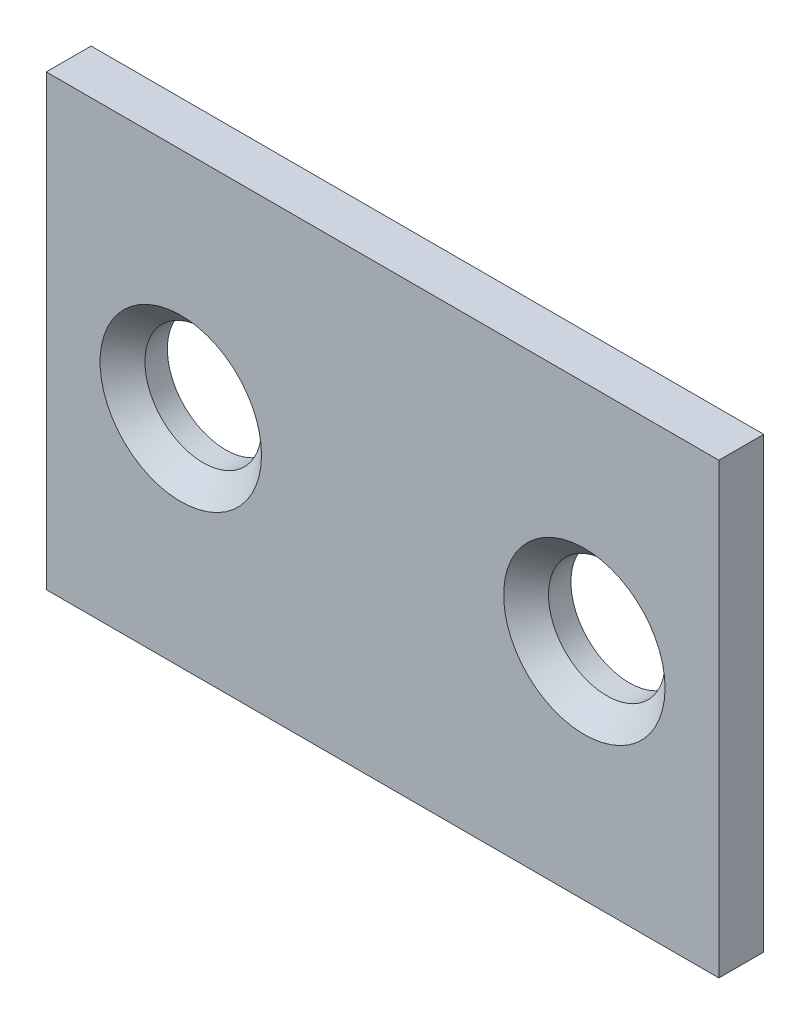
SolidWorks part; units mm, degrees
material "Декапирана стом. ламарина Iгр. 1c"
ref_plane "Front Plane" through (0, 0, 0) normal (0, 0, 1) x (1, 0, 0)
ref_plane "Top Plane" through (0, 0, 0) normal (0, 1, 0) x (1, 0, 0)
ref_plane "Right Plane" through (0, 0, 0) normal (1, 0, 0) x (0, 0, -1)
sketch "Sketch1" plane through (0, 0, 0) normal (0, 0, 1) x (1, 0, 0)
  line L1 (-15, -10) -> (15, -10)
  line L2 (-15, -10) -> (-15, 10)
  line L3 (-15, 10) -> (15, 10)
  line L4 (15, -10) -> (15, 10)
  line L5 (-15, -10) -> (15, 10) construction
  line L6 (-15, 10) -> (15, -10) construction
  point P0 (0, 0)
  dimension "D1" = 30
  dimension "D2" = 20
base flange "Base-Flange1" sketch "Sketch1" thickness 2 reverse thickness direction yes parameters "D1"=0.2286
hole_wizard "Ø5.2 (5.2) Diameter Hole1" positions "Sketch7" profile "Sketch6" hole size "Ø5.2" standard "DIN" end condition through all
sketch "Sketch7" plane through (0, 0, 2) normal (0, 0, 1) x (1, 0, 0)
  line L0 (-20.8376, 0) -> (24.0889, 0) construction
  line L2 (0, 16.98) -> (0, -16.5602) construction
  point P0 (-9, 0)
  dimension "D1" = 18
sketch "Sketch6" plane through (-9, 0, 2) normal (1, 0, 0) x (0, -1, 0)
  line L0 (0, 0) -> (0, 2)
  line L1 (0, 2) -> (2.6, 2)
  line L2 (2.6, 2) -> (2.6, 1)
  line L3 (2.6, 1) -> (3.6, 0)
  line L5 (3.6, 0) -> (0, 0)
  line L6 (-2.6, 1) -> (-3.6, 0) construction
  line L11 (0, -6.35) -> (0, 107.95) construction
  dimension "Thru Hole Dia." = 5.2
  dimension "Thru Hole Depth" = 2
  dimension "Near C'Sink Dia." = 7.2
  dimension "Near C'Sink Angle" = 90
mirror "Mirror1" about plane through (0, 0, 0) normal (1, 0, 0) of "Ø5.2 (5.2) Diameter Hole1"
sketch "Bend-Lines1" [suppressed] plane through (0, 0, 0) normal (0, 1, 0) x (1, 0, 0)
sketch "Bounding-Box1" [suppressed] plane through (0, 0, 0) normal (0, 1, 0) x (1, 0, 0)
sheet metal parameters "Sheet-Metal7" thickness 2 parameters "D1"=0.2286
flat pattern "Flat-Pattern7" [suppressed]
sketch "Bend-Lines2" plane through (0, 0, 0) normal (0, 1, 0) x (1, 0, 0)
sketch3d "Bounding-Box2" [suppressed]
  line L0 (-15, -10, 0) -> (15, -10, 0) construction
  line L1 (-15, 10, 0) -> (15, 10, 0) construction
  line L2 (-15, -10, 0) -> (-15, 10, 0) construction
  line L3 (15, -10, 0) -> (15, 10, 0) construction
sheet metal parameters "Sheet-Metal8" thickness 2 parameters "D1"=0.2286
flat pattern "Flat-Pattern7"
sketch "Bend-Lines2" plane through (0, 0, 0) normal (0, 1, 0) x (1, 0, 0)
sketch3d "Bounding-Box2" [suppressed]
  line L0 (15, -10, 0) -> (-15, -10, 0) construction
  line L1 (15, 10, 0) -> (-15, 10, 0) construction
  line L2 (15, -10, 0) -> (15, 10, 0) construction
  line L3 (-15, -10, 0) -> (-15, 10, 0) construction
sheet metal parameters "Sheet-Metal9" thickness 2 parameters "D1"=0.2286
flat pattern "Flat-Pattern7"
sketch "Bend-Lines2" plane through (0, 0, 0) normal (0, 1, 0) x (1, 0, 0)
sketch3d "Bounding-Box2" [suppressed]
  line L0 (15, -10, 0) -> (-15, -10, 0) construction
  line L1 (15, 10, 0) -> (-15, 10, 0) construction
  line L2 (15, -10, 0) -> (15, 10, 0) construction
  line L3 (-15, -10, 0) -> (-15, 10, 0) construction
